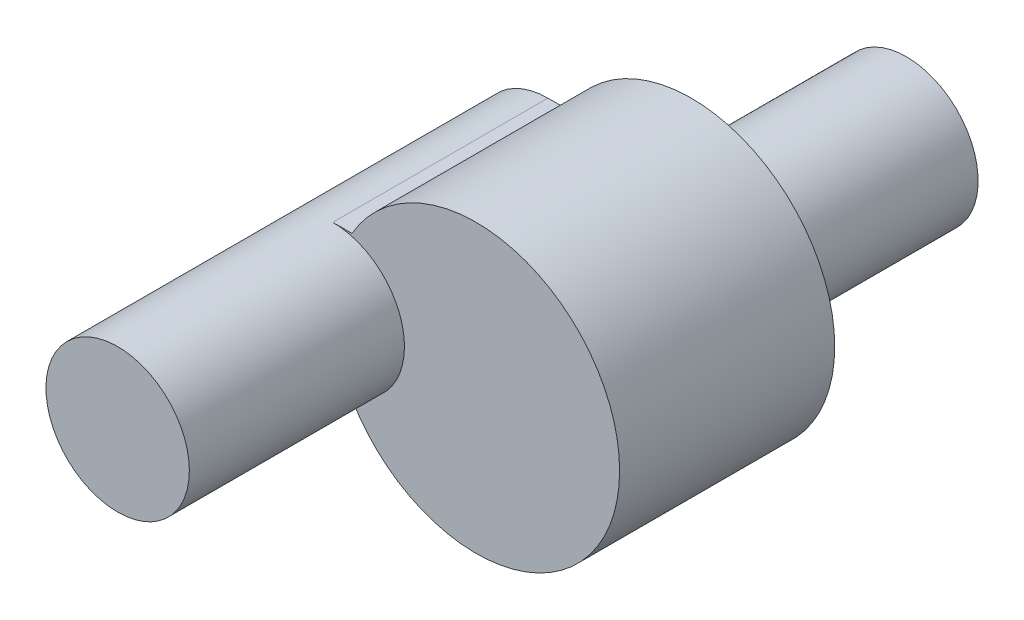
SolidWorks part; units mm, degrees
ref_plane "Спереди" through (0, 0, 0) normal (0, 0, 1) x (1, 0, 0)
ref_plane "Сверху" through (0, 0, 0) normal (0, 1, 0) x (1, 0, 0)
ref_plane "Справа" through (0, 0, 0) normal (1, 0, 0) x (0, 0, -1)
other "Configuration Table"
sketch "Sketch1" plane through (0, 0, 0) normal (0, 0, 1) x (1, 0, 0)
  line L0 (-0.5652, 4.3904) -> (-10.6356, 4.3904) construction
  line L5 (-8.7387, 5.3904) -> (-8.4707, 5.3904)
  line L6 (-8.7387, 3.3904) -> (-8.4707, 3.3904)
  circle A3 centre (-8.7387, 4.3904) radius 1
  circle A7 centre (-6.7387, 4.3904) radius 2
  point P0 (-6.5763, 4.3904)
  dimension "D1" = 4
  dimension "D2" = 2
  dimension "D3" = 2
  dimension "D4" = 2
extrude "Boss-Extrude1" add sketch "Sketch1" along normal blind 3 contours A7 L0 A3 L6 | L0 A7 L5 A3 | A3 L0 | L0 A7 | A7 L0 | A3 region at (-6.5459, 3.4834, 0) region at (-6.5459, 5.2974, 0) region at (-8.5444, 5.3808, 0) region at (-8.5444, 3.4, 0) region at (-9.1149, 3.935, 0)
ref_plane "Plane1" through (0, 0, 3) normal (0, 0, 1) x (1, 0, 0)
sketch "Sketch2" plane through (0, 0, 3) normal (0, 0, 1) x (1, 0, 0)
  circle A0 centre (-8.7387, 4.3904) radius 1
  arc A2 (-8.7387, 5.3904) -> (-8.7387, 3.3904) centre (-8.7387, 4.3904) ccw construction
extrude "Boss-Extrude2" add sketch "Sketch2" along normal blind 3
ref_plane "Plane2" through (0, 0, 0) normal (0, 0, -1) x (-1, 0, 0)
sketch "Sketch3" plane through (0, 0, 0) normal (0, 0, -1) x (-1, 0, 0)
  circle A0 centre (6.7387, 4.3904) radius 1
  circle A1 centre (8.7387, 4.3904) radius 1 construction
extrude "Boss-Extrude3" add sketch "Sketch3" along normal blind 3
equation "\"R small\"= 2"
equation "\"R big\"= 4"
equation "\"width\"= 0.6"
equation "\"border width\"= 1"
equation "\"D1@Sketch1\"=\"R big\""
equation "\"D2@Sketch1\"=\"R small\""
equation "\"D3@Sketch1\"=\"R small\""
equation "\"depth\"= 3"
